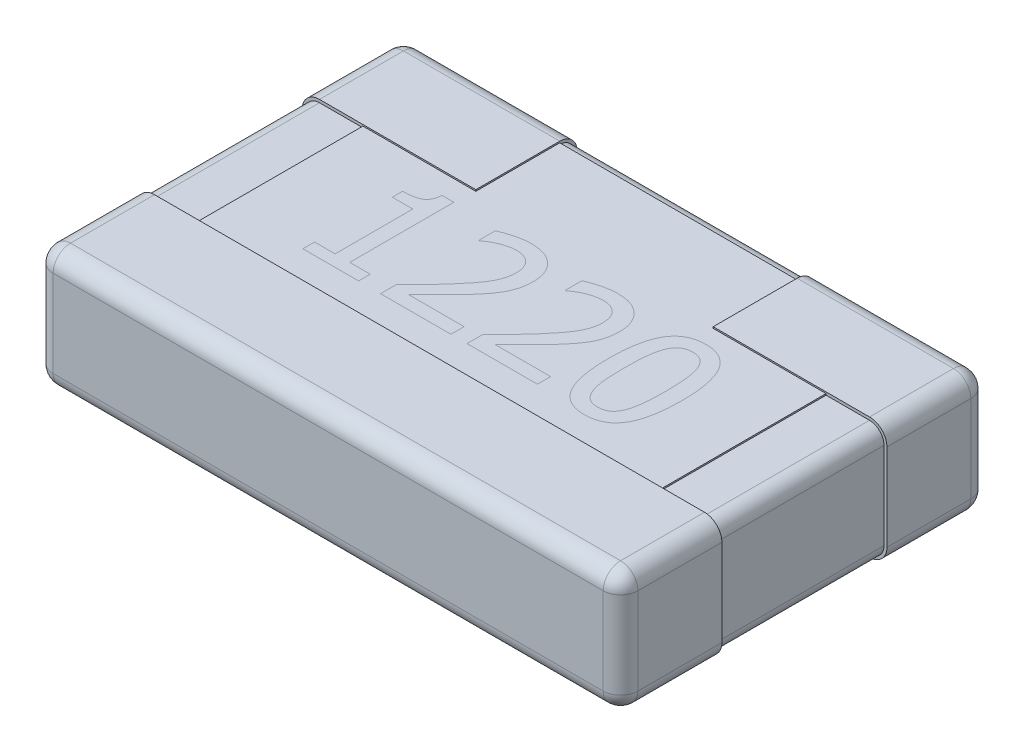
SolidWorks part; units mm, degrees
ref_plane "Front Plane" through (0, 0, 0) normal (0, 0, 1) x (1, 0, 0)
ref_plane "Top Plane" through (0, 0, 0) normal (0, 1, 0) x (1, 0, 0)
ref_plane "Right Plane" through (0, 0, 0) normal (1, 0, 0) x (0, 0, -1)
sketch "Sketch1" plane through (0, 0, 0) normal (0, 1, 0) x (1, 0, 0)
  line L1 (-1, 0.625) -> (1, 0.625)
  line L2 (-1, 0.625) -> (-1, -0.625)
  line L3 (-1, -0.625) -> (1, -0.625)
  line L4 (1, 0.625) -> (1, -0.625)
  line L5 (-1, 0.625) -> (1, -0.625) construction
  line L6 (-1, -0.625) -> (1, 0.625) construction
  point P0 (0, 0)
  dimension "D1" = 2
  dimension "D2" = 1.25
extrude "Boss-Extrude1" add sketch "Sketch1" along normal blind 0.4
sketch "Sketch2" plane through (0, 0, 0) normal (0, -1, 0) x (1, 0, 0)
  line L0 (0, 0.625) -> (0, -0.625) construction
  line L1 (-1.01, 0.635) -> (1.01, 0.635)
  line L2 (-1.01, 0.635) -> (-1.01, 0.285)
  line L3 (-1.01, 0.285) -> (1.01, 0.285)
  line L4 (1.01, 0.635) -> (1.01, 0.285)
  line L5 (-1, 0.625) -> (1, 0.625) construction
  line L6 (1, -0.625) -> (-1, -0.625) construction
  line L7 (-1, 0) -> (1, 0) construction
  line L8 (-1, -0.625) -> (-1, 0.625) construction
  line L9 (1, 0.625) -> (1, -0.625) construction
  line L10 (1.01, -0.285) -> (0.41, -0.285)
  line L11 (-1.01, -0.635) -> (-0.41, -0.635)
  line L12 (-1.01, -0.635) -> (-1.01, -0.285)
  line L13 (-1.01, -0.285) -> (-0.41, -0.285)
  line L14 (-0.41, -0.635) -> (-0.41, -0.285)
  line L15 (0.41, -0.635) -> (0.41, -0.285)
  line L16 (1.01, -0.635) -> (0.41, -0.635)
  line L17 (1.01, -0.635) -> (1.01, -0.285)
  dimension "D1" = 0.01
  dimension "D2" = 0.01
  dimension "D3" = 0.35
  dimension "D4" = 0.01
  dimension "D5" = 0.6
  dimension "D6" = 0.35
extrude "Boss-Extrude2" add sketch "Sketch2" along normal blind 0.01
sketch "Sketch3" plane through (0, 0, 0) normal (0, -1, 0) x (1, 0, 0)
  line L4 (1.01, 0.635) -> (-1.01, 0.635)
  line L5 (1.01, 0.285) -> (1.01, 0.635)
  line L6 (-1.01, 0.285) -> (1.01, 0.285)
  line L7 (-1.01, 0.635) -> (-1.01, 0.285)
  line L8 (1.01, 0.635) -> (-1.01, 0.635)
  line L9 (1.01, 0.285) -> (1.01, 0.635)
  line L10 (-1.01, 0.285) -> (1.01, 0.285)
  line L11 (-1.01, 0.635) -> (-1.01, 0.285)
  line L12 (-1.01, -0.635) -> (-0.41, -0.635)
  line L13 (-0.41, -0.635) -> (-0.41, -0.285)
  line L14 (-0.41, -0.285) -> (-1.01, -0.285)
  line L15 (-1.01, -0.285) -> (-1.01, -0.635)
  line L16 (-1.01, -0.635) -> (-0.41, -0.635)
  line L17 (-0.41, -0.635) -> (-0.41, -0.285)
  line L18 (-0.41, -0.285) -> (-1.01, -0.285)
  line L19 (-1.01, -0.285) -> (-1.01, -0.635)
  line L20 (1.01, -0.285) -> (0.41, -0.285)
  line L21 (0.41, -0.285) -> (0.41, -0.635)
  line L22 (0.41, -0.635) -> (1.01, -0.635)
  line L23 (1.01, -0.635) -> (1.01, -0.285)
  line L24 (1.01, -0.285) -> (0.41, -0.285)
  line L25 (0.41, -0.285) -> (0.41, -0.635)
  line L26 (0.41, -0.635) -> (1.01, -0.635)
  line L27 (1.01, -0.635) -> (1.01, -0.285)
  dimension "D1" = 0
  dimension "D2" = 0
  dimension "D3" = 0
extrude "Boss-Extrude3" add sketch "Sketch3" against normal blind 0.41
sketch "Sketch4" plane through (0, 0.4, 0) normal (0, 1, 0) x (1, 0, 0)
  line L0 (1, -0.285) -> (-1, -0.285) construction
  line L1 (-0.8, -0.285) -> (0.8, -0.285)
  line L2 (-0.8, -0.285) -> (-0.8, 0.575)
  line L3 (-0.8, 0.575) -> (0.8, 0.575)
  line L4 (0.8, -0.285) -> (0.8, 0.575)
  line L5 (0, 0) -> (0, 0.7031) construction
  line L6 (0.41, 0.625) -> (-0.41, 0.625) construction
  point P9 (0, 0)
  dimension "D1" = 1.6
  dimension "D2" = 0.05
extrude "Boss-Extrude4" add sketch "Sketch4" along normal blind 0.005
fillet "Fillet1" radius 0.05 6 edges at (0, 0, -0.625) (1, 0, 0) (1, 0.4, 0) (0, 0.4, -0.625) (-1, 0, 0) (-1, 0.4, 0)
fillet "Fillet2" radius 0.06 18 edges at (0.71, -0.01, -0.635) (1.01, 0.2, -0.635) (0.71, 0.41, -0.635) (1.01, 0.41, -0.46) (1.01, -0.01, -0.46) (1.01, -0.01, 0.46) (1.01, 0.41, 0.46) (1.01, 0.2, 0.635) (-1.01, -0.01, 0.46) (0, -0.01, 0.635) (-1.01, 0.2, 0.635) (0, 0.41, 0.635) (-1.01, 0.41, 0.46) (-0.71, -0.01, -0.635) (-1.01, -0.01, -0.46) (-1.01, 0.2, -0.635) (-0.71, 0.41, -0.635) (-1.01, 0.41, -0.46)
sketch "Sketch5" plane through (0, 0.405, 0) normal (0, 1, 0) x (1, 0, 0)
  line L0 (-0.8, -0.1856) -> (0.8, -0.1856) construction
  line L1 (-0.8, 0.285) -> (-0.8, -0.285) construction
  line L2 (0.8, -0.285) -> (0.8, 0.285) construction
  text T0 "1220" font "Tahoma" height 0.4
wrap "Wrap1" sketch "Sketch5" wrap type scribe source sketch "Sketch5"
